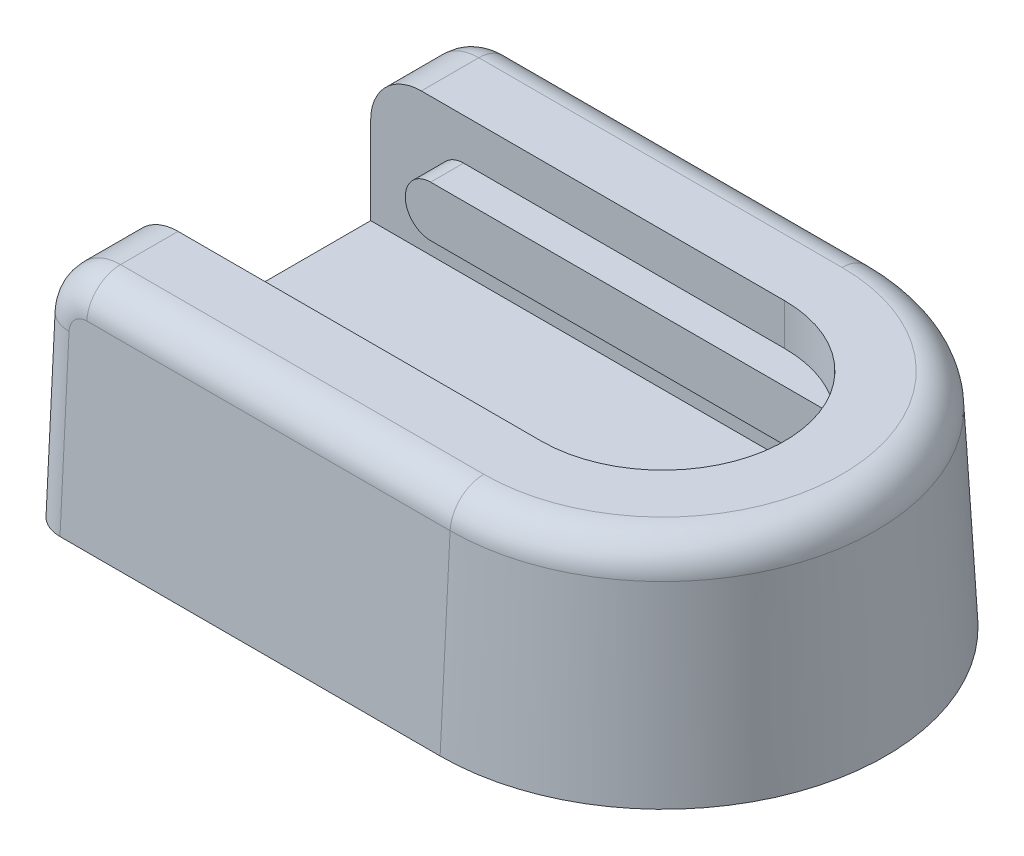
SolidWorks part; units mm, degrees
material "EPDM 60 Durometer"
ref_plane "Front Plane" through (0, 0, 0) normal (0, 0, 1) x (1, 0, 0)
ref_plane "Top Plane" through (0, 0, 0) normal (0, 1, 0) x (1, 0, 0)
ref_plane "Right Plane" through (0, 0, 0) normal (1, 0, 0) x (0, 0, -1)
sketch "Sketch1" plane through (0, 0, 0) normal (0, 1, 0) x (1, 0, 0)
  line L0 (0, 0) -> (24.5, 0)
  line L1 (0, 0) -> (0, 25)
  line L2 (0, 25) -> (24.5, 25)
  arc A0 (24.5, 25) -> (24.5, 0) centre (24.5, 12.5) cw
  point P5 (37, 12.5)
  dimension "D1" = 25
  dimension "D2" = 37
extrude "Boss-Extrude1" add sketch "Sketch1" along normal blind 13.15
sketch "Sketch2" plane through (0, 13.15, 0) normal (0, 1, 0) x (1, 0, 0)
  line L0 (0, 19.7) -> (24.5, 19.7)
  line L1 (0, 25) -> (0, 0) construction
  line L2 (0, 19.7) -> (0, 5.3)
  line L3 (0, 5.3) -> (24.5, 5.3)
  line L4 (0, 25) -> (0, 0)
  arc A0 (24.5, 5.3) -> (24.5, 19.7) centre (24.5, 12.5) ccw
  arc A1 (24.5, 0) -> (24.5, 25) centre (24.5, 12.5) ccw construction
  point P4 (0, 12.5)
  point P7 (0, 12.5)
  point P9 (31.7, 12.5)
  line M3 (0, 25) -> (0, 0)
  dimension "D1" = 14.4
extrude "Cut-Extrude1" cut sketch "Sketch2" against normal blind 8.15 contours L3 A0 L0 M3 region at (15.1203, 13.15, -12.5)
sketch "Sketch3" plane through (0, 5, 0) normal (0, 1, 0) x (1, 0, 0)
  line L0 (0, 5.3) -> (24.5, 5.3) construction
  line L1 (0, 19.7) -> (24.5, 19.7) construction
  line L2 (4, 5.3) -> (24.5, 5.3)
  line L3 (4, 19.7) -> (24.5, 19.7)
  line L6 (29.4272, 17.75) -> (4, 17.75)
  line L7 (-968.5, 12.5) -> (49031.5, 12.5) construction
  line L8 (29.4272, 7.25) -> (4, 7.25)
  line L9 (4, 7.25) -> (4, 5.3)
  line L11 (4, 17.75) -> (4, 19.7)
  arc A0 (24.5, 5.3) -> (24.5, 19.7) centre (24.5, 12.5) ccw construction
  arc A1 (24.5, 5.3) -> (29.4272, 7.25) centre (24.5, 12.5) ccw
  arc A2 (29.4272, 17.75) -> (24.5, 19.7) centre (24.5, 12.5) ccw
  dimension "D1" = 1.95
  dimension "D2" = 4
extrude "Boss-Extrude3" add sketch "Sketch3" along normal blind 3 from offset 2.7
fillet "Fillet1" radius 1.5 4 edges at (4, 7.7, -6.275) (4, 10.7, -6.275) (4, 7.7, -18.725) (4, 10.7, -18.725)
draft "Draft2" type of draft neutral plane draft angle 3 faces to draft 3 face at (12.25, 6.575, -25) face at (30.75, 6.575, -12.5) face at (12.25, 6.575, 0) neutral plane through (24.5, 13.15, -12.5) neutral plane normal (0, 1, 0) parameters "D1"=3
fillet "Fillet2" radius 3 2 edges at (0, 13.15, -22.35) (0, 13.15, -2.65)
fillet "Fillet3" radius 2 7 edges at (0, 5.075, 0.4232) (0.8787, 12.2713, 0.046) (0, 5.075, -25.4232) (0.8787, 12.2713, -25.046) (13.75, 13.15, -25) (37, 13.15, -12.5) (13.75, 13.15, 0)
